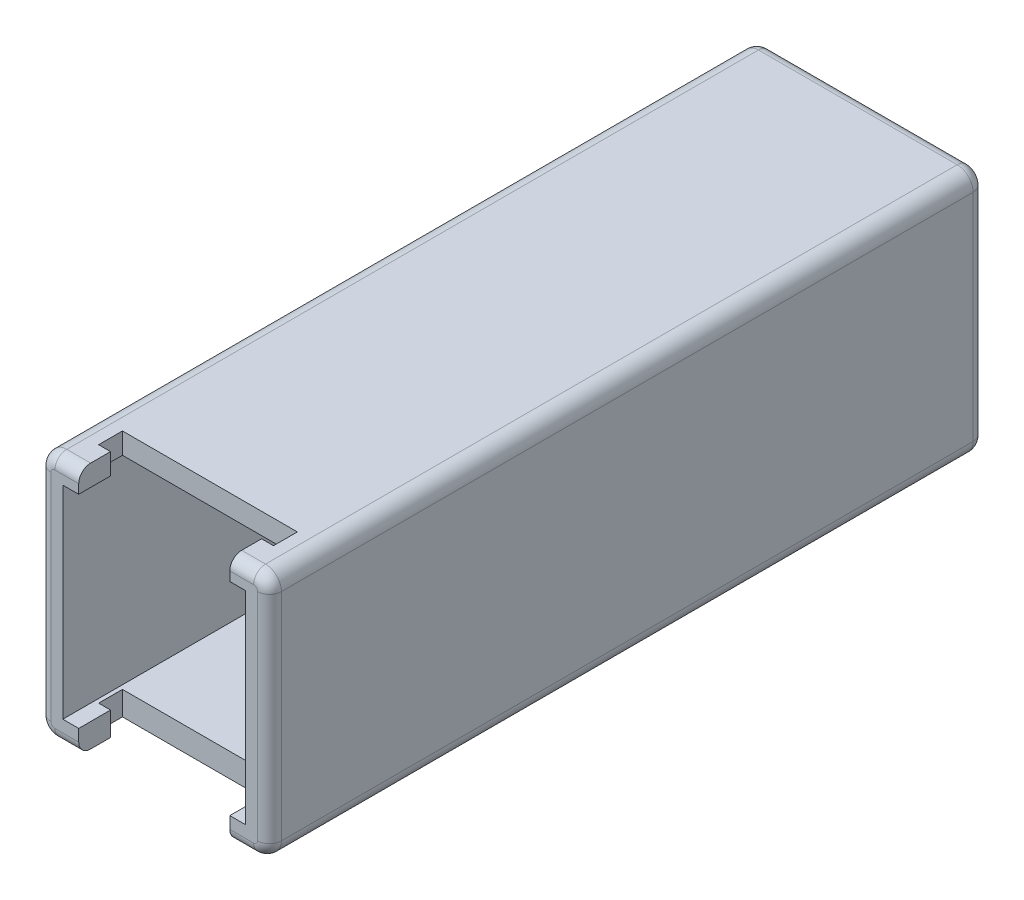
SolidWorks part; units mm, degrees
ref_plane "정면" through (0, 0, 0) normal (0, 0, 1) x (1, 0, 0)
ref_plane "윗면" through (0, 0, 0) normal (0, 1, 0) x (1, 0, 0)
ref_plane "우측면" through (0, 0, 0) normal (1, 0, 0) x (0, 0, -1)
sketch "스케치1" plane through (0, 0, 0) normal (0, 0, 1) x (1, 0, 0)
  line L2 (11.5, 12.75) -> (11.5, -12.75)
  line L3 (11.5, -12.75) -> (-11.5, -12.75)
  line L4 (-11.5, 12.75) -> (-11.5, -12.75)
  line L5 (11.5, 12.75) -> (-11.5, -12.75) construction
  line L6 (11.5, -12.75) -> (-11.5, 12.75) construction
  line L7 (-14.5, 15.4012) -> (-14.5, -15.75)
  line L8 (14.5, -15.75) -> (-14.5, -15.75)
  line L9 (14.5, 15.4012) -> (14.5, -15.75)
  line L10 (-11.5, 12.75) -> (11.5, 12.75)
  line L11 (-14.5, 15.4012) -> (14.5, 15.4012)
  arc A2 (14.5, 15.4012) -> (-14.5, 15.4012) centre (0, -90.7625) ccw construction
  arc A4 (11.5, 12.75) -> (-11.5, 12.75) centre (0, -90.7625) ccw construction
  point P0 (0, 0)
  dimension "D1" = 25.5
  dimension "D2" = 23
  dimension "D3" = 3
extrude "보스-돌출1" add sketch "스케치1" along normal blind 90
extrude "보스-돌출2" add sketch "스케치1<2>" along normal blind 2 contours L2 L4 L3 region at (0, 0, 0)
sketch "스케치1<2>" plane through (0, 0, 0) normal (0, 0, 1) x (1, 0, 0) same geometry as "스케치1"
sketch "스케치2" plane through (0, 0, 0) normal (0, 0, -1) x (-1, 0, 0)
  line L0 (0, 0) -> (0, -14.25) construction
  line L1 (-4, -12.75) -> (4, -12.75)
  line L2 (-4, -12.75) -> (-4, -15.75)
  line L3 (-4, -15.75) -> (4, -15.75)
  line L4 (4, -12.75) -> (4, -15.75)
  line L5 (-4, -12.75) -> (4, -15.75) construction
  line L6 (-4, -15.75) -> (4, -12.75) construction
  line L7 (14.5, -15.75) -> (-14.5, -15.75) construction
  point P0 (0, -14.25)
  dimension "D1" = 8
  dimension "D2" = 3
extrude "컷-돌출1" cut sketch "스케치2" against normal blind 10
sketch "스케치3" plane through (0, 0, 0) normal (0, 1, 0) x (1, 0, 0)
  line L0 (-9.5, -90) -> (-9.5, -86)
  line L1 (14.5, -90) -> (-14.5, -90) construction
  line L2 (-9.5, -86) -> (-11, -86)
  line L3 (-11, -86) -> (-11, -83)
  line L4 (-11, -83) -> (11, -83)
  line L5 (0, -83) -> (0, -90) construction
  line L6 (9.5, -90) -> (-9.5, -90)
  line L7 (11, -86) -> (11, -83)
  line L8 (9.5, -86) -> (11, -86)
  line L9 (9.5, -90) -> (9.5, -86)
  dimension "D1" = 4
  dimension "D2" = 1.5
  dimension "D3" = 3
  dimension "D4" = 22
extrude "컷-돌출2" cut sketch "스케치3" against normal through all both and the other way through all
fillet "필렛1" radius 2 4 edges at (-14.5, -15.75, 45) (14.5, -15.75, 45) (14.5, 15.4012, 45) (-14.5, 15.4012, 45)
fillet "필렛2" radius 1.5 19 edges at (11, -15.75, 90) (13.9142, -15.1642, 90) (11, 15.4012, 90) (13.9142, 14.8154, 90) (-11, 15.4012, 90) (-13.9142, 14.8154, 90) (-11, -15.75, 90) (-13.9142, -15.1642, 90) (8.25, -15.75, 0) (13.9142, -15.1642, 0) (14.5, -0.1744, 0) (13.9142, 14.8154, 0) (-8.25, -15.75, 0) (-13.9142, -15.1642, 0) (-14.5, -0.1744, 0) (-13.9142, 14.8154, 0) (14.5, -0.1744, 90) (-14.5, -0.1744, 90) (0, 15.4012, 0)
